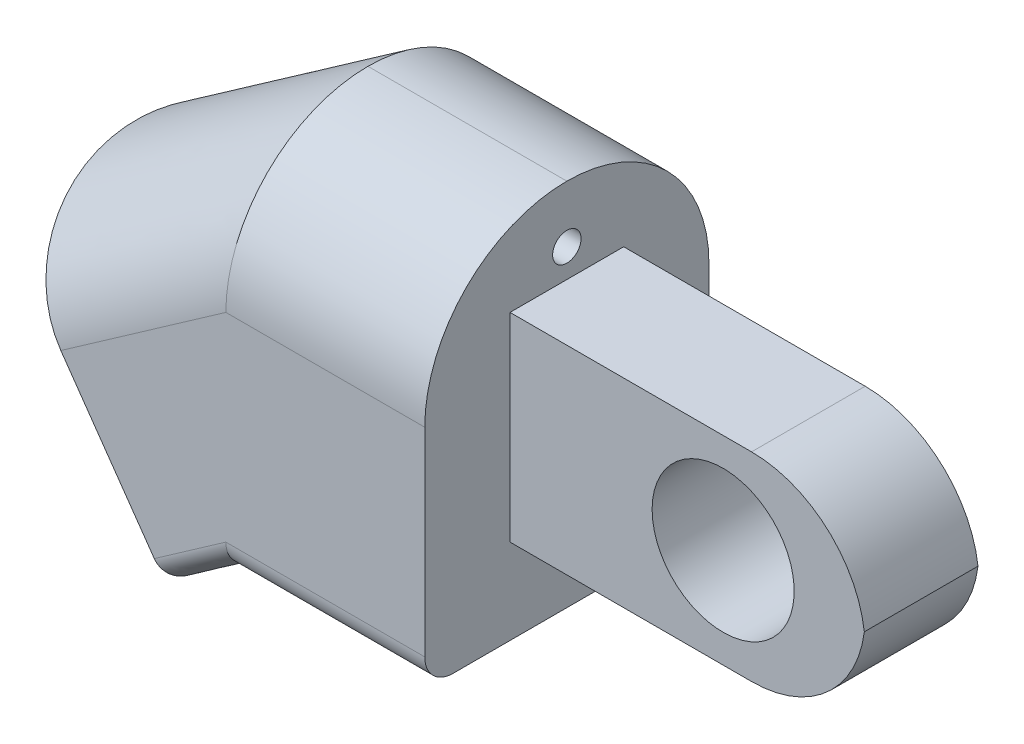
SolidWorks part; units mm, degrees
material "PLA"
ref_plane "Front" through (0, 0, 0) normal (0, 0, 1) x (1, 0, 0)
ref_plane "Top" through (0, 0, 0) normal (0, 1, 0) x (1, 0, 0)
ref_plane "Right" through (0, 0, 0) normal (1, 0, 0) x (0, 0, -1)
sketch "Sketch1" plane through (0, 0, 0) normal (0, 0, 1) x (1, 0, 0)
  line L1 (-6.35, 4.445) -> (9.525, 4.445)
  line L2 (-6.35, 4.445) -> (-6.35, -4.445)
  line L3 (-6.35, -4.445) -> (9.525, -4.445)
  line L4 (9.525, 4.445) -> (9.525, -4.445)
  circle A0 centre (0, 0) radius 3.175
  dimension "D1" = 6.35
  dimension "D2" = 6.35
  dimension "D3" = 4.445
  dimension "D4" = 4.445
  dimension "D5" = 15.875
extrude "Boss-Extrude1" add sketch "Sketch1" along normal blind 5.08
fillet "Fillet1" radius 5.08 2 edges at (-6.35, -4.445, 2.54) (-6.35, 4.445, 2.54)
sketch "Sketch2" plane through (9.525, 0, 0) normal (1, 0, 0) x (0, 0, -1)
  line L0 (-8.89, -8.255) -> (3.81, -8.255)
  line L1 (3.81, -8.255) -> (3.81, 8.255)
  line L2 (3.81, 8.255) -> (-8.89, 8.255)
  line L3 (-8.89, 8.255) -> (-8.89, -8.255)
  line L4 (0, -4.445) -> (0, 4.445)
  line L5 (0, 4.445) -> (-5.08, 4.445)
  line L6 (-5.08, 4.445) -> (-5.08, -4.445)
  line L7 (-5.08, -4.445) -> (0, -4.445)
  line L8 (0, -4.445) -> (0, 4.445)
  line L9 (0, 4.445) -> (-5.08, 4.445)
  line L10 (-5.08, 4.445) -> (-5.08, -4.445)
  line L11 (-5.08, -4.445) -> (0, -4.445)
  line M5 (0, -4.445) -> (0, 4.445)
  line M6 (0, 4.445) -> (-5.08, 4.445)
  line M7 (-5.08, 4.445) -> (-5.08, -4.445)
  line M8 (-5.08, -4.445) -> (0, -4.445)
  dimension "D1" = 0
  dimension "D2" = 3.81
extrude "Boss-Extrude2" add sketch "Sketch2" along normal blind 8.89 separate body contours L2 L3 L0 L1 M5 M8 M7 M6 | M8 M5 M6 M7 | L8 L9 L10 L11
ref_plane "Plane1" through (13.97, 0, 0) normal (-1, 0, 0) x (0, 0, 1)
mirror "Mirror7" about plane through (13.97, 0, 0) normal (-1, 0, 0) of bodies 101
fillet "Fillet3" radius 6.35 2 edges at (13.97, 8.255, -3.81) (13.97, 8.255, 8.89)
sketch "Sketch3" plane through (0, 4.445, 0) normal (0, 1, 0) x (1, 0, 0)
  line L4 (9.525, 0) -> (-1.27, 0)
  line L5 (-1.27, 0) -> (-1.27, -5.08)
  line L6 (-1.27, -5.08) -> (9.525, -5.08)
  line L7 (9.525, -5.08) -> (9.525, 0)
  line L12 (9.525, 0) -> (-1.27, 0)
  line L13 (-1.27, 0) -> (-1.27, -5.08)
  line L14 (-1.27, -5.08) -> (9.525, -5.08)
  line L15 (9.525, -5.08) -> (9.525, 0)
  dimension "D1" = 0
extrude "Boss-Extrude3" add sketch "Sketch3" along normal blind 2.54
sketch "Sketch4" plane through (-1.27, 0, 0) normal (-1, 0, 0) x (0, 0, 1)
  line L8 (5.08, 6.985) -> (5.08, 4.445) construction
  line L9 (0, 4.445) -> (5.08, 4.445) construction
  circle A0 centre (2.54, 5.715) radius 0.635
  dimension "D1" = 1.27
  dimension "D2" = 1.27
  dimension "D3" = 2.54
extrude "Cut-Extrude1" cut sketch "Sketch4" against normal through all
fillet "Fillet6" radius 1.27 2 edges at (13.97, -8.255, -3.81) (13.97, -8.255, 8.89)
sketch "Sketch5" plane through (0, -8.255, 0) normal (0, -1, 0) x (1, 0, 0)
  line L0 (18.415, 1.905) -> (18.415, 3.175) construction
  line L1 (18.415, 7.62) -> (9.525, 7.62)
  line L2 (18.415, 7.62) -> (18.415, -2.54)
  line L3 (18.415, -2.54) -> (9.525, -2.54)
  line L4 (9.525, 7.62) -> (9.525, -2.54)
  line L5 (16.51, 5.4203) -> (17.78, 5.4203)
  line L6 (17.78, 5.4203) -> (18.415, 6.5201)
  line L7 (18.415, 6.5201) -> (17.78, 7.62)
  line L8 (17.78, 7.62) -> (16.51, 7.62)
  line L9 (16.51, 7.62) -> (15.875, 6.5201)
  line L10 (15.875, 6.5201) -> (16.51, 5.4203)
  line L11 (13.97, 5.4203) -> (15.24, 5.4203)
  line L12 (15.24, 5.4203) -> (15.875, 6.5201)
  line L13 (15.875, 6.5201) -> (15.24, 7.62)
  line L14 (15.24, 7.62) -> (13.97, 7.62)
  line L15 (13.97, 7.62) -> (13.335, 6.5201)
  line L16 (13.335, 6.5201) -> (13.97, 5.4203)
  line L17 (11.43, 5.4203) -> (12.7, 5.4203)
  line L18 (12.7, 5.4203) -> (13.335, 6.5201)
  line L19 (13.335, 6.5201) -> (12.7, 7.62)
  line L20 (12.7, 7.62) -> (11.43, 7.62)
  line L21 (11.43, 7.62) -> (10.795, 6.5201)
  line L22 (10.795, 6.5201) -> (11.43, 5.4203)
  line L23 (8.89, 5.4203) -> (10.16, 5.4203)
  line L24 (10.16, 5.4203) -> (10.795, 6.5201)
  line L25 (10.795, 6.5201) -> (10.16, 7.62)
  line L26 (10.16, 7.62) -> (8.89, 7.62)
  line L27 (8.89, 7.62) -> (8.255, 6.5201)
  line L28 (8.255, 6.5201) -> (8.89, 5.4203)
  line L29 (6.35, 5.4203) -> (7.62, 5.4203)
  line L30 (7.62, 5.4203) -> (8.255, 6.5201)
  line L31 (8.255, 6.5201) -> (7.62, 7.62)
  line L32 (7.62, 7.62) -> (6.35, 7.62)
  line L33 (6.35, 7.62) -> (5.715, 6.5201)
  line L34 (5.715, 6.5201) -> (6.35, 5.4203)
  line L35 (3.81, 5.4203) -> (5.08, 5.4203)
  line L36 (5.08, 5.4203) -> (5.715, 6.5201)
  line L37 (5.715, 6.5201) -> (5.08, 7.62)
  line L38 (5.08, 7.62) -> (3.81, 7.62)
  line L39 (3.81, 7.62) -> (3.175, 6.5201)
  line L40 (3.175, 6.5201) -> (3.81, 5.4203)
  line L41 (1.27, 5.4203) -> (2.54, 5.4203)
  line L42 (2.54, 5.4203) -> (3.175, 6.5201)
  line L43 (3.175, 6.5201) -> (2.54, 7.62)
  line L44 (2.54, 7.62) -> (1.27, 7.62)
  line L45 (1.27, 7.62) -> (0.635, 6.5201)
  line L46 (0.635, 6.5201) -> (1.27, 5.4203)
  line L47 (-1.27, 5.4203) -> (0, 5.4203)
  line L48 (0, 5.4203) -> (0.635, 6.5201)
  line L49 (0.635, 6.5201) -> (0, 7.62)
  line L50 (0, 7.62) -> (-1.27, 7.62)
  line L51 (-1.27, 7.62) -> (-1.905, 6.5201)
  line L52 (-1.905, 6.5201) -> (-1.27, 5.4203)
  line L53 (-3.81, 5.4203) -> (-2.54, 5.4203)
  line L54 (-2.54, 5.4203) -> (-1.905, 6.5201)
  line L55 (-1.905, 6.5201) -> (-2.54, 7.62)
  line L56 (-2.54, 7.62) -> (-3.81, 7.62)
  line L57 (-3.81, 7.62) -> (-4.445, 6.5201)
  line L58 (-4.445, 6.5201) -> (-3.81, 5.4203)
  line L59 (-6.35, 5.4203) -> (-5.08, 5.4203)
  line L60 (-5.08, 5.4203) -> (-4.445, 6.5201)
  line L61 (-4.445, 6.5201) -> (-5.08, 7.62)
  line L62 (-5.08, 7.62) -> (-6.35, 7.62)
  line L63 (-6.35, 7.62) -> (-6.985, 6.5201)
  line L64 (-6.985, 6.5201) -> (-6.35, 5.4203)
  line L65 (13.97, 3.0835) -> (15.24, 3.0835)
  line L66 (15.24, 3.0835) -> (15.875, 4.1833)
  line L67 (15.875, 4.1833) -> (15.24, 5.2832)
  line L68 (15.24, 5.2832) -> (13.97, 5.2832)
  line L69 (13.97, 5.2832) -> (13.335, 4.1833)
  line L70 (13.335, 4.1833) -> (13.97, 3.0835)
  line L71 (11.43, 3.0835) -> (12.7, 3.0835)
  line L72 (12.7, 3.0835) -> (13.335, 4.1833)
  line L73 (13.335, 4.1833) -> (12.7, 5.2832)
  line L74 (12.7, 5.2832) -> (11.43, 5.2832)
  line L75 (11.43, 5.2832) -> (10.795, 4.1833)
  line L76 (10.795, 4.1833) -> (11.43, 3.0835)
  line L77 (8.89, 3.0835) -> (10.16, 3.0835)
  line L78 (10.16, 3.0835) -> (10.795, 4.1833)
  line L79 (10.795, 4.1833) -> (10.16, 5.2832)
  line L80 (10.16, 5.2832) -> (8.89, 5.2832)
  line L81 (8.89, 5.2832) -> (8.255, 4.1833)
  line L82 (8.255, 4.1833) -> (8.89, 3.0835)
  line L83 (6.35, 3.0835) -> (7.62, 3.0835)
  line L84 (7.62, 3.0835) -> (8.255, 4.1833)
  line L85 (8.255, 4.1833) -> (7.62, 5.2832)
  line L86 (7.62, 5.2832) -> (6.35, 5.2832)
  line L87 (6.35, 5.2832) -> (5.715, 4.1833)
  line L88 (5.715, 4.1833) -> (6.35, 3.0835)
  line L89 (3.81, 3.0835) -> (5.08, 3.0835)
  line L90 (5.08, 3.0835) -> (5.715, 4.1833)
  line L91 (5.715, 4.1833) -> (5.08, 5.2832)
  line L92 (5.08, 5.2832) -> (3.81, 5.2832)
  line L93 (3.81, 5.2832) -> (3.175, 4.1833)
  line L94 (3.175, 4.1833) -> (3.81, 3.0835)
  line L95 (1.27, 3.0835) -> (2.54, 3.0835)
  line L96 (2.54, 3.0835) -> (3.175, 4.1833)
  line L97 (3.175, 4.1833) -> (2.54, 5.2832)
  line L98 (2.54, 5.2832) -> (1.27, 5.2832)
  line L99 (1.27, 5.2832) -> (0.635, 4.1833)
  line L100 (0.635, 4.1833) -> (1.27, 3.0835)
  line L101 (-1.27, 3.0835) -> (0, 3.0835)
  line L102 (0, 3.0835) -> (0.635, 4.1833)
  line L103 (0.635, 4.1833) -> (0, 5.2832)
  line L104 (0, 5.2832) -> (-1.27, 5.2832)
  line L105 (-1.27, 5.2832) -> (-1.905, 4.1833)
  line L106 (-1.905, 4.1833) -> (-1.27, 3.0835)
  line L107 (-3.81, 3.0835) -> (-2.54, 3.0835)
  line L108 (-2.54, 3.0835) -> (-1.905, 4.1833)
  line L109 (-1.905, 4.1833) -> (-2.54, 5.2832)
  line L110 (-2.54, 5.2832) -> (-3.81, 5.2832)
  line L111 (-3.81, 5.2832) -> (-4.445, 4.1833)
  line L112 (-4.445, 4.1833) -> (-3.81, 3.0835)
  line L113 (-6.35, 3.0835) -> (-5.08, 3.0835)
  line L114 (-5.08, 3.0835) -> (-4.445, 4.1833)
  line L115 (-4.445, 4.1833) -> (-5.08, 5.2832)
  line L116 (-5.08, 5.2832) -> (-6.35, 5.2832)
  line L117 (-6.35, 5.2832) -> (-6.985, 4.1833)
  line L118 (-6.985, 4.1833) -> (-6.35, 3.0835)
  line L119 (13.97, 0.7467) -> (15.24, 0.7467)
  line L120 (15.24, 0.7467) -> (15.875, 1.8465)
  line L121 (15.875, 1.8465) -> (15.24, 2.9464)
  line L122 (15.24, 2.9464) -> (13.97, 2.9464)
  line L123 (13.97, 2.9464) -> (13.335, 1.8465)
  line L124 (13.335, 1.8465) -> (13.97, 0.7467)
  line L125 (11.43, 0.7467) -> (12.7, 0.7467)
  line L126 (12.7, 0.7467) -> (13.335, 1.8465)
  line L127 (13.335, 1.8465) -> (12.7, 2.9464)
  line L128 (12.7, 2.9464) -> (11.43, 2.9464)
  line L129 (11.43, 2.9464) -> (10.795, 1.8465)
  line L130 (10.795, 1.8465) -> (11.43, 0.7467)
  line L131 (8.89, 0.7467) -> (10.16, 0.7467)
  line L132 (10.16, 0.7467) -> (10.795, 1.8465)
  line L133 (10.795, 1.8465) -> (10.16, 2.9464)
  line L134 (10.16, 2.9464) -> (8.89, 2.9464)
  line L135 (8.89, 2.9464) -> (8.255, 1.8465)
  line L136 (8.255, 1.8465) -> (8.89, 0.7467)
  line L137 (6.35, 0.7467) -> (7.62, 0.7467)
  line L138 (7.62, 0.7467) -> (8.255, 1.8465)
  line L139 (8.255, 1.8465) -> (7.62, 2.9464)
  line L140 (7.62, 2.9464) -> (6.35, 2.9464)
  line L141 (6.35, 2.9464) -> (5.715, 1.8465)
  line L142 (5.715, 1.8465) -> (6.35, 0.7467)
  line L143 (3.81, 0.7467) -> (5.08, 0.7467)
  line L144 (5.08, 0.7467) -> (5.715, 1.8465)
  line L145 (5.715, 1.8465) -> (5.08, 2.9464)
  line L146 (5.08, 2.9464) -> (3.81, 2.9464)
  line L147 (3.81, 2.9464) -> (3.175, 1.8465)
  line L148 (3.175, 1.8465) -> (3.81, 0.7467)
  line L149 (1.27, 0.7467) -> (2.54, 0.7467)
  line L150 (2.54, 0.7467) -> (3.175, 1.8465)
  line L151 (3.175, 1.8465) -> (2.54, 2.9464)
  line L152 (2.54, 2.9464) -> (1.27, 2.9464)
  line L153 (1.27, 2.9464) -> (0.635, 1.8465)
  line L154 (0.635, 1.8465) -> (1.27, 0.7467)
  line L155 (-1.27, 0.7467) -> (0, 0.7467)
  line L156 (0, 0.7467) -> (0.635, 1.8465)
  line L157 (0.635, 1.8465) -> (0, 2.9464)
  line L158 (0, 2.9464) -> (-1.27, 2.9464)
  line L159 (-1.27, 2.9464) -> (-1.905, 1.8465)
  line L160 (-1.905, 1.8465) -> (-1.27, 0.7467)
  line L161 (-3.81, 0.7467) -> (-2.54, 0.7467)
  line L162 (-2.54, 0.7467) -> (-1.905, 1.8465)
  line L163 (-1.905, 1.8465) -> (-2.54, 2.9464)
  line L164 (-2.54, 2.9464) -> (-3.81, 2.9464)
  line L165 (-3.81, 2.9464) -> (-4.445, 1.8465)
  line L166 (-4.445, 1.8465) -> (-3.81, 0.7467)
  line L167 (-6.35, 0.7467) -> (-5.08, 0.7467)
  line L168 (-5.08, 0.7467) -> (-4.445, 1.8465)
  line L169 (-4.445, 1.8465) -> (-5.08, 2.9464)
  line L170 (-5.08, 2.9464) -> (-6.35, 2.9464)
  line L171 (-6.35, 2.9464) -> (-6.985, 1.8465)
  line L172 (-6.985, 1.8465) -> (-6.35, 0.7467)
  line L173 (13.97, -1.5901) -> (15.24, -1.5901)
  line L174 (15.24, -1.5901) -> (15.875, -0.4903)
  line L175 (15.875, -0.4903) -> (15.24, 0.6096)
  line L176 (15.24, 0.6096) -> (13.97, 0.6096)
  line L177 (13.97, 0.6096) -> (13.335, -0.4903)
  line L178 (13.335, -0.4903) -> (13.97, -1.5901)
  line L179 (11.43, -1.5901) -> (12.7, -1.5901)
  line L180 (12.7, -1.5901) -> (13.335, -0.4903)
  line L181 (13.335, -0.4903) -> (12.7, 0.6096)
  line L182 (12.7, 0.6096) -> (11.43, 0.6096)
  line L183 (11.43, 0.6096) -> (10.795, -0.4903)
  line L184 (10.795, -0.4903) -> (11.43, -1.5901)
  line L185 (8.89, -1.5901) -> (10.16, -1.5901)
  line L186 (10.16, -1.5901) -> (10.795, -0.4903)
  line L187 (10.795, -0.4903) -> (10.16, 0.6096)
  line L188 (10.16, 0.6096) -> (8.89, 0.6096)
  line L189 (8.89, 0.6096) -> (8.255, -0.4903)
  line L190 (8.255, -0.4903) -> (8.89, -1.5901)
  line L191 (6.35, -1.5901) -> (7.62, -1.5901)
  line L192 (7.62, -1.5901) -> (8.255, -0.4903)
  line L193 (8.255, -0.4903) -> (7.62, 0.6096)
  line L194 (7.62, 0.6096) -> (6.35, 0.6096)
  line L195 (6.35, 0.6096) -> (5.715, -0.4903)
  line L196 (5.715, -0.4903) -> (6.35, -1.5901)
  line L197 (3.81, -1.5901) -> (5.08, -1.5901)
  line L198 (5.08, -1.5901) -> (5.715, -0.4903)
  line L199 (5.715, -0.4903) -> (5.08, 0.6096)
  line L200 (5.08, 0.6096) -> (3.81, 0.6096)
  line L201 (3.81, 0.6096) -> (3.175, -0.4903)
  line L202 (3.175, -0.4903) -> (3.81, -1.5901)
  line L203 (1.27, -1.5901) -> (2.54, -1.5901)
  line L204 (2.54, -1.5901) -> (3.175, -0.4903)
  line L205 (3.175, -0.4903) -> (2.54, 0.6096)
  line L206 (2.54, 0.6096) -> (1.27, 0.6096)
  line L207 (1.27, 0.6096) -> (0.635, -0.4903)
  line L208 (0.635, -0.4903) -> (1.27, -1.5901)
  line L209 (-1.27, -1.5901) -> (0, -1.5901)
  line L210 (0, -1.5901) -> (0.635, -0.4903)
  line L211 (0.635, -0.4903) -> (0, 0.6096)
  line L212 (0, 0.6096) -> (-1.27, 0.6096)
  line L213 (-1.27, 0.6096) -> (-1.905, -0.4903)
  line L214 (-1.905, -0.4903) -> (-1.27, -1.5901)
  line L215 (-3.81, -1.5901) -> (-2.54, -1.5901)
  line L216 (-2.54, -1.5901) -> (-1.905, -0.4903)
  line L217 (-1.905, -0.4903) -> (-2.54, 0.6096)
  line L218 (-2.54, 0.6096) -> (-3.81, 0.6096)
  line L219 (-3.81, 0.6096) -> (-4.445, -0.4903)
  line L220 (-4.445, -0.4903) -> (-3.81, -1.5901)
  line L221 (-6.35, -1.5901) -> (-5.08, -1.5901)
  line L222 (-5.08, -1.5901) -> (-4.445, -0.4903)
  line L223 (-4.445, -0.4903) -> (-5.08, 0.6096)
  line L224 (-5.08, 0.6096) -> (-6.35, 0.6096)
  line L225 (-6.35, 0.6096) -> (-6.985, -0.4903)
  line L226 (-6.985, -0.4903) -> (-6.35, -1.5901)
  line L227 (13.97, -3.9269) -> (15.24, -3.9269)
  line L228 (15.24, -3.9269) -> (15.875, -2.8271)
  line L229 (15.875, -2.8271) -> (15.24, -1.7272)
  line L230 (15.24, -1.7272) -> (13.97, -1.7272)
  line L231 (13.97, -1.7272) -> (13.335, -2.8271)
  line L232 (13.335, -2.8271) -> (13.97, -3.9269)
  line L233 (11.43, -3.9269) -> (12.7, -3.9269)
  line L234 (12.7, -3.9269) -> (13.335, -2.8271)
  line L235 (13.335, -2.8271) -> (12.7, -1.7272)
  line L236 (12.7, -1.7272) -> (11.43, -1.7272)
  line L237 (11.43, -1.7272) -> (10.795, -2.8271)
  line L238 (10.795, -2.8271) -> (11.43, -3.9269)
  line L239 (8.89, -3.9269) -> (10.16, -3.9269)
  line L240 (10.16, -3.9269) -> (10.795, -2.8271)
  line L241 (10.795, -2.8271) -> (10.16, -1.7272)
  line L242 (10.16, -1.7272) -> (8.89, -1.7272)
  line L243 (8.89, -1.7272) -> (8.255, -2.8271)
  line L244 (8.255, -2.8271) -> (8.89, -3.9269)
  line L245 (6.35, -3.9269) -> (7.62, -3.9269)
  line L246 (7.62, -3.9269) -> (8.255, -2.8271)
  line L247 (8.255, -2.8271) -> (7.62, -1.7272)
  line L248 (7.62, -1.7272) -> (6.35, -1.7272)
  line L249 (6.35, -1.7272) -> (5.715, -2.8271)
  line L250 (5.715, -2.8271) -> (6.35, -3.9269)
  line L251 (3.81, -3.9269) -> (5.08, -3.9269)
  line L252 (5.08, -3.9269) -> (5.715, -2.8271)
  line L253 (5.715, -2.8271) -> (5.08, -1.7272)
  line L254 (5.08, -1.7272) -> (3.81, -1.7272)
  line L255 (3.81, -1.7272) -> (3.175, -2.8271)
  line L256 (3.175, -2.8271) -> (3.81, -3.9269)
  line L257 (1.27, -3.9269) -> (2.54, -3.9269)
  line L258 (2.54, -3.9269) -> (3.175, -2.8271)
  line L259 (3.175, -2.8271) -> (2.54, -1.7272)
  line L260 (2.54, -1.7272) -> (1.27, -1.7272)
  line L261 (1.27, -1.7272) -> (0.635, -2.8271)
  line L262 (0.635, -2.8271) -> (1.27, -3.9269)
  line L263 (-1.27, -3.9269) -> (0, -3.9269)
  line L264 (0, -3.9269) -> (0.635, -2.8271)
  line L265 (0.635, -2.8271) -> (0, -1.7272)
  line L266 (0, -1.7272) -> (-1.27, -1.7272)
  line L267 (-1.27, -1.7272) -> (-1.905, -2.8271)
  line L268 (-1.905, -2.8271) -> (-1.27, -3.9269)
  line L269 (-3.81, -3.9269) -> (-2.54, -3.9269)
  line L270 (-2.54, -3.9269) -> (-1.905, -2.8271)
  line L271 (-1.905, -2.8271) -> (-2.54, -1.7272)
  line L272 (-2.54, -1.7272) -> (-3.81, -1.7272)
  line L273 (-3.81, -1.7272) -> (-4.445, -2.8271)
  line L274 (-4.445, -2.8271) -> (-3.81, -3.9269)
  line L275 (-6.35, -3.9269) -> (-5.08, -3.9269)
  line L276 (-5.08, -3.9269) -> (-4.445, -2.8271)
  line L277 (-4.445, -2.8271) -> (-5.08, -1.7272)
  line L278 (-5.08, -1.7272) -> (-6.35, -1.7272)
  line L279 (-6.35, -1.7272) -> (-6.985, -2.8271)
  line L280 (-6.985, -2.8271) -> (-6.35, -3.9269)
  line L281 (16.51, 3.0835) -> (17.78, 3.0835)
  line L282 (17.78, 3.0835) -> (18.415, 4.1833)
  line L283 (18.415, 4.1833) -> (17.78, 5.2832)
  line L284 (17.78, 5.2832) -> (16.51, 5.2832)
  line L285 (16.51, 5.2832) -> (15.875, 4.1833)
  line L286 (15.875, 4.1833) -> (16.51, 3.0835)
  line L287 (16.51, 0.7467) -> (17.78, 0.7467)
  line L288 (17.78, 0.7467) -> (18.415, 1.8465)
  line L289 (18.415, 1.8465) -> (17.78, 2.9464)
  line L290 (17.78, 2.9464) -> (16.51, 2.9464)
  line L291 (16.51, 2.9464) -> (15.875, 1.8465)
  line L292 (15.875, 1.8465) -> (16.51, 0.7467)
  line L293 (16.51, -1.5901) -> (17.78, -1.5901)
  line L294 (17.78, -1.5901) -> (18.415, -0.4903)
  line L295 (18.415, -0.4903) -> (17.78, 0.6096)
  line L296 (17.78, 0.6096) -> (16.51, 0.6096)
  line L297 (16.51, 0.6096) -> (15.875, -0.4903)
  line L298 (15.875, -0.4903) -> (16.51, -1.5901)
  line L299 (16.51, -3.9269) -> (17.78, -3.9269)
  line L300 (17.78, -3.9269) -> (18.415, -2.8271)
  line L301 (18.415, -2.8271) -> (17.78, -1.7272)
  line L302 (17.78, -1.7272) -> (16.51, -1.7272)
  line L303 (16.51, -1.7272) -> (15.875, -2.8271)
  line L304 (15.875, -2.8271) -> (16.51, -3.9269)
  circle A0 centre (17.145, 6.5201) radius 1.0999 construction
  dimension "D1" = 2.54
  dimension "D2" = 10
  dimension "D3" = 5
extrude "Boss-Extrude7" [suppressed] add sketch "Sketch5" along normal blind 0.381 contours L9 L10 L5 L6 L7 L1 | L21 L22 L17 L18 L19 L1 | L33 L34 L29 L30 L31 L1 | L45 L46 L41 L42 L43 L1 | L57 L58 L53 L54 L55 L1 | L65 L66 L67 L68 L69 L70 | L77 L78 L79 L80 L81 L82 | L89 L90 L91 L92 L93 L94 | L101 L102 L103 L104 L105 L106 | L113 L114 L115 L116 L117 L118 | L287 L288 L289 L290 L291 L292 | L125 L126 L127 L128 L129 L130 | L137 L138 L139 L140 L141 L142 | L149 L150 L151 L152 L153 L154 | L161 L162 L163 L164 L165 L166 | L173 L174 L175 L176 L177 L178 | L185 L186 L187 L188 L189 L190 | L197 L198 L199 L200 L201 L202 | L209 L210 L211 L212 L213 L214 | L221 L222 L223 L224 L225 L226
fillet "Fillet7" radius 1.905 2 edges at (4.1275, 6.985, 0) (4.1275, 6.985, 5.08)
sketch "Sketch8" plane through (9.525, 0, 0) normal (-1, 0, 0) x (0, 0, 1)
  line L1 (12.1816, -9.6255) -> (-11.0828, -9.6255)
  line L2 (12.1816, -9.6255) -> (12.1816, 9.4268)
  line L3 (12.1816, 9.4268) -> (-11.0828, 9.4268)
  line L4 (-11.0828, -9.6255) -> (-11.0828, 9.4268)
extrude "Cut-Extrude3" cut sketch "Sketch8" along normal through all
ref_plane "Plane3" through (2.5128, 1.7595, 0) normal (-0.8192, -0.5736, 0) x (0, 0, -1)
sketch "Sketch9" plane through (2.5128, 1.7595, 0) normal (-0.8192, -0.5736, 0) x (0, 0, -1)
  line L3 (3.81, 3.9028) -> (3.81, 11.1851)
  line L4 (2.54, 12.2254) -> (-7.62, 12.2254)
  line L5 (-8.89, 11.1851) -> (-8.89, 3.9028)
  line L6 (3.81, 3.9028) -> (3.81, 11.1851)
  line L7 (2.54, 12.2254) -> (-7.62, 12.2254)
  line L8 (-8.89, 11.1851) -> (-8.89, 3.9028)
  ellipse E0 centre (-2.54, 0.7819) end of major axis (-1.905, 0.7819) minor radius 0.5202 construction
  ellipse E1 centre (-2.54, 0.7819) end of major axis (-1.905, 0.7819) minor radius 0.5202
  ellipse E4 centre (2.54, 11.1851) end of major axis (3.81, 11.1851) minor radius 1.0403 (3.81, 11.1851) -> (2.54, 12.2254) ccw
  ellipse E5 centre (-7.62, 11.1851) end of major axis (-8.89, 11.1851) minor radius 1.0403 (-7.62, 12.2254) -> (-8.89, 11.1851) ccw
  ellipse E6 centre (-2.54, 3.9028) end of major axis (-8.89, 3.9028) minor radius 5.2016 (-8.89, 3.9028) -> (-2.54, -1.2988) ccw
  ellipse E7 centre (-2.54, 3.9028) end of major axis (-8.89, 3.9028) minor radius 5.2016 (-2.54, -1.2988) -> (3.81, 3.9028) ccw
  ellipse E8 centre (2.54, 11.1851) end of major axis (3.81, 11.1851) minor radius 1.0403 (3.81, 11.1851) -> (2.54, 12.2254) ccw
  ellipse E9 centre (-7.62, 11.1851) end of major axis (-8.89, 11.1851) minor radius 1.0403 (-7.62, 12.2254) -> (-8.89, 11.1851) ccw
  ellipse E10 centre (-2.54, 3.9028) end of major axis (-8.89, 3.9028) minor radius 5.2016 (-8.89, 3.9028) -> (-2.54, -1.2988) ccw
  ellipse E11 centre (-2.54, 3.9028) end of major axis (-8.89, 3.9028) minor radius 5.2016 (-2.54, -1.2988) -> (3.81, 3.9028) ccw
  dimension "D1" = 0
extrude "Boss-Extrude9" add sketch "Sketch9" against normal up to surface (5.8275 mm away)
sketch "Sketch10" plane through (2.5128, 1.7595, 0) normal (-0.8192, -0.5736, 0) x (0, 0, 1)
  line L0 (7.62, -12.2254) -> (-2.54, -12.2254) construction
  line L1 (-3.81, -3.9028) -> (-3.81, -11.1851) construction
  line L2 (1.1629, -10.0062) -> (0.816, -10.3773)
  line L3 (0.816, -10.3773) -> (0.9309, -9.8825)
  line L4 (0.6313, -9.6826) -> (0.2186, -9.9788)
  line L5 (0.2186, -9.9788) -> (0.4278, -9.5159)
  line L6 (0.1729, -9.2615) -> (-0.2896, -9.4715)
  line L7 (-0.2896, -9.4715) -> (0.006, -9.0583)
  line L8 (-0.1944, -8.759) -> (-0.689, -8.8748)
  line L9 (-0.689, -8.8748) -> (-0.3185, -8.5272)
  line L10 (-0.4566, -8.1946) -> (-0.9644, -8.2116)
  line L11 (-0.9644, -8.2116) -> (-0.5332, -7.943)
  line L12 (-0.6037, -7.5898) -> (-1.105, -7.5075)
  line L13 (-1.105, -7.5075) -> (-0.6297, -7.3281)
  line L14 (-0.63, -6.9679) -> (-1.1056, -6.7894)
  line L15 (-1.1056, -6.7894) -> (-0.6045, -6.7062)
  line L16 (-0.5345, -6.3529) -> (-0.9661, -6.085)
  line L17 (-0.9661, -6.085) -> (-0.4584, -6.1012)
  line L18 (-0.3208, -5.7683) -> (-0.6919, -5.4214)
  line L19 (-0.6919, -5.4214) -> (-0.197, -5.5363)
  line L20 (0.0028, -5.2367) -> (-0.2934, -4.824)
  line L21 (-0.2934, -4.824) -> (0.1695, -5.0333)
  line L22 (0.4239, -4.7784) -> (0.2139, -4.3158)
  line L23 (0.2139, -4.3158) -> (0.6271, -4.6114)
  line L24 (0.9264, -4.411) -> (0.8106, -3.9164)
  line L25 (0.8106, -3.9164) -> (1.1582, -4.2869)
  line L26 (1.4908, -4.1488) -> (1.4738, -3.6411)
  line L27 (1.4738, -3.6411) -> (1.7424, -4.0722)
  line L28 (2.0956, -4.0017) -> (2.178, -3.5004)
  line L29 (2.178, -3.5004) -> (2.3573, -3.9757)
  line L30 (2.7175, -3.9754) -> (2.896, -3.4998)
  line L31 (2.896, -3.4998) -> (2.9792, -4.0009)
  line L32 (3.3325, -4.0709) -> (3.6004, -3.6393)
  line L33 (3.6004, -3.6393) -> (3.5842, -4.147)
  line L34 (3.9171, -4.2846) -> (4.264, -3.9135)
  line L35 (4.264, -3.9135) -> (4.1491, -4.4084)
  line L36 (4.4487, -4.6082) -> (4.8614, -4.312)
  line L37 (4.8614, -4.312) -> (4.6522, -4.7749)
  line L38 (4.9071, -5.0294) -> (5.3696, -4.8193)
  line L39 (5.3696, -4.8193) -> (5.074, -5.2325)
  line L40 (5.2744, -5.5318) -> (5.769, -5.416)
  line L41 (5.769, -5.416) -> (5.3985, -5.7636)
  line L42 (5.5366, -6.0963) -> (6.0444, -6.0792)
  line L43 (6.0444, -6.0792) -> (5.6132, -6.3478)
  line L44 (5.6837, -6.701) -> (6.185, -6.7834)
  line L45 (6.185, -6.7834) -> (5.7097, -6.9627)
  line L46 (5.71, -7.3229) -> (6.1856, -7.5014)
  line L47 (6.1856, -7.5014) -> (5.6845, -7.5846)
  line L48 (5.6145, -7.9379) -> (6.0461, -8.2058)
  line L49 (6.0461, -8.2058) -> (5.5384, -8.1896)
  line L50 (5.4008, -8.5225) -> (5.7719, -8.8695)
  line L51 (5.7719, -8.8695) -> (5.277, -8.7545)
  line L52 (5.0772, -9.0542) -> (5.3734, -9.4668)
  line L53 (5.3734, -9.4668) -> (4.9105, -9.2576)
  line L54 (4.6561, -9.5125) -> (4.8661, -9.975)
  line L55 (4.8661, -9.975) -> (4.4529, -9.6795)
  line L56 (4.1536, -9.8798) -> (4.2694, -10.3744)
  line L57 (4.2694, -10.3744) -> (3.9218, -10.004)
  line L58 (3.5892, -10.1421) -> (3.6062, -10.6498)
  line L59 (3.6062, -10.6498) -> (3.3376, -10.2186)
  line L60 (2.9844, -10.2892) -> (2.902, -10.7904)
  line L61 (2.902, -10.7904) -> (2.7227, -10.3152)
  line L62 (2.3625, -10.3155) -> (2.184, -10.791)
  line L63 (2.184, -10.791) -> (2.1008, -10.2899)
  line L64 (1.7475, -10.2199) -> (1.4796, -10.6515)
  line L65 (1.4796, -10.6515) -> (1.4958, -10.1438)
  circle A0 centre (2.54, -7.1454) radius 3.175
  ellipse M5 centre (2.54, -3.9028) end of major axis (8.89, -3.9028) minor radius 5.2016 (8.89, -3.9028) -> (-3.81, -3.9028) ccw
  line M6 (-3.81, -3.9028) -> (-3.81, -11.1851)
  ellipse M7 centre (-2.54, -11.1851) end of major axis (-1.27, -11.1851) minor radius 1.0403 (-3.81, -11.1851) -> (-2.54, -12.2254) ccw
  line M8 (-2.54, -12.2254) -> (7.62, -12.2254)
  ellipse M9 centre (7.62, -11.1851) end of major axis (8.89, -11.1851) minor radius 1.0403 (7.62, -12.2254) -> (8.89, -11.1851) ccw
  line M10 (8.89, -11.1851) -> (8.89, -3.9028)
  dimension "D1" = 6.35
  dimension "D2" = 5.08
  dimension "D3" = 6.35
  dimension "D4" = 30
  dimension "D5" = 0.508
  dimension "D6" = 32
extrude "Boss-Extrude10" add sketch "Sketch10" along normal blind 3.175 contours A0 L60 L61 L62 L63 L64 L65 L2 L3 L4 L5 L6 L7 L8 L9 L10 L11 L12 L13 L14 L15 L16 L17 L18 L19 L20 L21 L22 L23 L24 M10 M5 M6 M7 M8 M9 | L58 L59
sketch "Sketch11" plane through (2.5128, 1.7595, 0) normal (-0.8192, -0.5736, 0) x (0, 0, 1)
  circle A0 centre (2.54, -7.1454) radius 1.905
  dimension "D1" = 3.81
extrude "Cut-Extrude4" cut sketch "Sketch11" against normal blind 5.08
